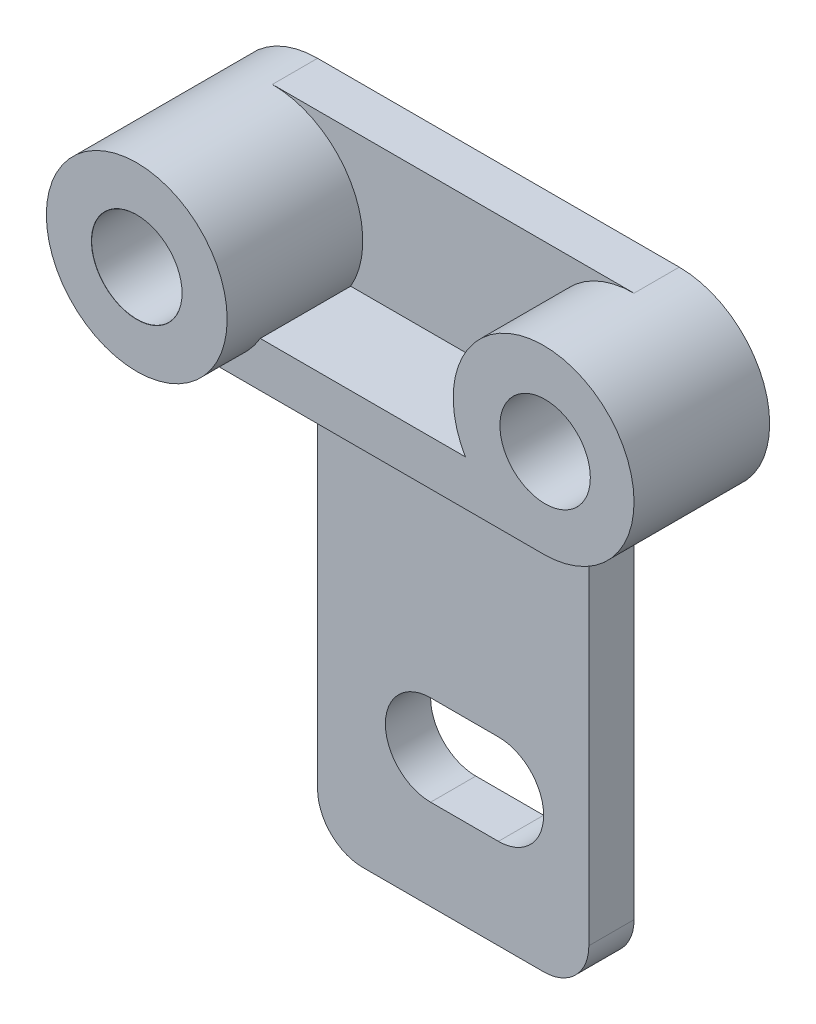
SolidWorks part; units mm, degrees
ref_plane "Front Plane" through (0, 0, 0) normal (0, 0, 1) x (1, 0, 0)
ref_plane "Top Plane" through (0, 0, 0) normal (0, 1, 0) x (1, 0, 0)
ref_plane "Right Plane" through (0, 0, 0) normal (1, 0, 0) x (0, 0, -1)
sketch "Sketch1" plane through (0, 0, 0) normal (0, 0, 1) x (1, 0, 0)
  circle A0 centre (-40, 0) radius 20
  circle A1 centre (40, 0) radius 20
  point P4 (0, 0)
  dimension "D1" = 40
  dimension "D2" = 40
  dimension "D3" = 40
  dimension "D4" = 80
extrude "Boss-Extrude1" add sketch "Sketch1" along normal blind 40 contours A0
extrude "Boss-Extrude2" add sketch "Sketch1<3>" along normal blind 30 separate body contours A1
sketch "Sketch1<3>" plane through (0, 0, 0) normal (0, 0, 1) x (1, 0, 0) same geometry as "Sketch1"
sketch "Sketch2" plane through (0, 0, 0) normal (0, 0, -1) x (-1, 0, 0)
  line L1 (-40, 20) -> (40, 20)
  line L2 (-40, 20) -> (-40, -20)
  line L3 (-40, -20) -> (40, -20)
  line L4 (40, 20) -> (40, -20)
  circle A0 centre (-40, 0) radius 20 construction
  circle A1 centre (40, 0) radius 20 construction
  point P4 (0, 0)
  point P7 (0, 0)
  point P12 (0, 0)
extrude "Boss-Extrude3" add sketch "Sketch2" against normal blind 10
sketch "Sketch6" plane through (0, 0, 30) normal (0, 0, 1) x (1, 0, 0)
  line L0 (40, -20) -> (-40, -20) construction
  line L1 (-40, -10) -> (40, -10)
  line L2 (-40, -10) -> (-40, -20)
  line L3 (-40, -20) -> (40, -20)
  line L4 (40, -10) -> (40, -20)
  circle A0 centre (40, 0) radius 20 construction
  point P4 (0, 0)
  dimension "D1" = 10
extrude "Boss-Extrude4" add sketch "Sketch6" against normal blind 30
hole_wizard "Ø20.0mm Dowel Hole1" positions "Sketch9" profile "Sketch10" hole size "Ø20.0" standard "ANSI Metric" end condition through all
sketch "Sketch9" plane through (0, 0, 40) normal (0, 0, 1) x (1, 0, 0)
  point P0 (-40, 0)
  point P3 (40.3314, -0.1774)
sketch "Sketch10" plane through (-40, 0, 40) normal (1, 0, 0) x (0, -1, 0)
  line L0 (0, 0) -> (0, 40)
  line L1 (0, 40) -> (10, 40)
  line L2 (10, 40) -> (10, 0.025)
  line L3 (10, 0.025) -> (10.025, 0)
  line L5 (10.025, 0) -> (0, 0)
  line L6 (-10, 0.025) -> (-10.025, 0) construction
  line L11 (0, -6.35) -> (0, 107.95) construction
  dimension "Thru Hole Dia." = 20
  dimension "Thru Hole Depth" = 40
  dimension "Near C'Sink Dia." = 20.05
  dimension "Near C'Sink Angle" = 90
sketch "Sketch11" plane through (0, 0, 0) normal (0, 0, -1) x (-1, 0, 0)
  line L0 (-40, -20) -> (40, -20) construction
  line L1 (-30, -20) -> (30, -20)
  line L2 (-30, -20) -> (-30, -120)
  line L3 (-30, -120) -> (30, -120)
  line L4 (30, -20) -> (30, -120)
  point P6 (0, 0)
  point P7 (0, 0)
  dimension "D1" = 60
  dimension "D2" = 100
  dimension "D3" = 30
extrude "Boss-Extrude5" add sketch "Sketch11" against normal blind 10
fillet "Fillet1" radius 10 1 edges at (-30, -120, 5)
fillet "Fillet2" radius 10 1 edges at (30, -120, 5)
sketch "Sketch12" plane through (0, 0, 10) normal (0, 0, 1) x (1, 0, 0)
  line L0 (-5, -90) -> (10, -90) construction
  line L1 (-5, -80) -> (10, -80)
  line L2 (-5, -100) -> (10, -100)
  line L3 (30, -20) -> (30, -110) construction
  line L4 (20, -120) -> (-20, -120) construction
  arc A0 (-5, -80) -> (-5, -100) centre (-5, -90) ccw
  arc A1 (10, -100) -> (10, -80) centre (10, -90) ccw
  point P2 (2.5, -90)
  dimension "D2" = 10
  dimension "D1" = 20
  dimension "D3" = 30
  dimension "D4" = 15
extrude "Cut-Extrude2" cut sketch "Sketch12" against normal up to next
equation "\"A\"=40"
